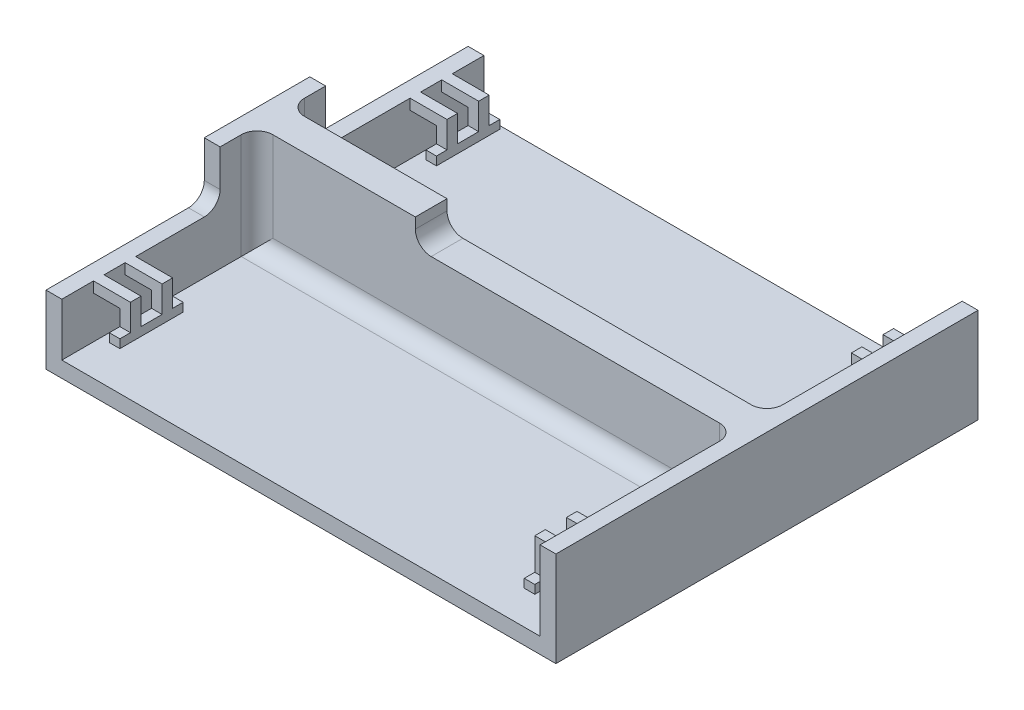
SolidWorks part; units mm, degrees
ref_plane "Piano frontale" through (0, 0, 0) normal (0, 0, 1) x (1, 0, 0)
ref_plane "Piano superiore" through (0, 0, 0) normal (0, 1, 0) x (1, 0, 0)
ref_plane "Piano destro" through (0, 0, 0) normal (1, 0, 0) x (0, 0, -1)
sketch "Schizzo1" plane through (0, 0, 0) normal (0, 0, 1) x (1, 0, 0)
  line L0 (11.7177, -12.3971) -> (506.3844, -12.3971) construction
  line L3 (25.2883, 10.9435) -> (25.2883, 30.9435)
  line L4 (118.9283, 25.9435) -> (118.9283, 7.9435)
  line L5 (118.9283, 7.9435) -> (22.2883, 7.9435)
  line L6 (115.9283, 25.9435) -> (115.9283, 10.9435)
  line L7 (115.9283, 10.9435) -> (25.2883, 10.9435)
  line L8 (22.2883, 7.9435) -> (22.2883, 30.9435)
  line L9 (22.2883, 30.9435) -> (25.2883, 30.9435)
  line L10 (115.9283, 25.9435) -> (118.9283, 25.9435)
  dimension "D1" = 90.64
  dimension "D2" = 20
  dimension "D3" = 15
  dimension "D4" = 3
extrude "Estrusione-Estrusione1" add sketch "Schizzo1" along normal blind 40
sketch "Schizzo2" plane through (25.2883, 0, 0) normal (1, 0, 0) x (0, 0, -1)
  line L0 (-40, 20.9435) -> (-10, 20.9435)
  line L1 (-40, 10.9435) -> (-40, 30.9435) construction
  line L2 (-10, 20.9435) -> (-10, 30.9435)
  line L3 (-40, 30.9435) -> (0, 30.9435) construction
  line L4 (-10, 30.9435) -> (-40, 30.9435)
  line L5 (-40, 30.9435) -> (-40, 20.9435)
  dimension "D1" = 30
  dimension "D2" = 10
extrude "Taglio-Estrusione2" cut sketch "Schizzo2" against normal blind 3
fillet "Raccordo1" radius 3 1 edges at (23.7883, 20.9435, 10)
sketch "Schizzo3" plane through (0, 0, 0) normal (0, 0, -1) x (-1, 0, 0)
  line L0 (-25.2883, 30.9435) -> (-55.2883, 30.9435)
  line L1 (-55.2883, 30.9435) -> (-55.2883, 25.9435)
  line L2 (-55.2883, 25.9435) -> (-115.9283, 25.9435)
  line L3 (-115.9283, 25.9435) -> (-115.9283, 10.9435)
  line L4 (-115.9283, 25.9435) -> (-115.9283, 10.9435) construction
  line L5 (-115.9283, 10.9435) -> (-25.2883, 10.9435) construction
  line L6 (-115.9283, 10.9435) -> (-25.2883, 10.9435)
  line L7 (-25.2883, 10.9435) -> (-25.2883, 30.9435)
  point P3 (-115.9283, 25.9435)
  dimension "D1" = 5
  dimension "D2" = 30
extrude "Estrusione-Estrusione2" add sketch "Schizzo3" against normal blind 3
mirror "Specchia1" about plane through (0, 0, 0) normal (0, 0, 1) of "Estrusione-Estrusione2", "Raccordo1", "Taglio-Estrusione2", "Estrusione-Estrusione1"
fillet "Raccordo2" radius 3 7 edges at (70.6083, 10.9435, 3) (70.6083, 10.9435, -3) (115.9283, 18.4435, -3) (115.9283, 18.4435, 3) (55.2883, 25.9435, 0) (25.2883, 20.9435, -3) (25.2883, 20.9435, 3)
sketch "Schizzo4" plane through (25.2883, 0, 0) normal (1, 0, 0) x (0, 0, -1)
  line L0 (-34, 20.9435) -> (-34, 18.9435)
  line L1 (-40, 20.9435) -> (-13, 20.9435) construction
  line L2 (-34, 18.9435) -> (-32, 18.9435)
  line L3 (-32, 18.9435) -> (-32, 20.9435)
  line L4 (-32, 20.9435) -> (-34, 20.9435)
  line L5 (-28, 20.9435) -> (-28, 18.9435)
  line L6 (-28, 18.9435) -> (-26, 18.9435)
  line L7 (-26, 18.9435) -> (-26, 20.9435)
  line L8 (-26, 20.9435) -> (-28, 20.9435)
  point P8 (-34.1109, 18.9435)
  dimension "D1" = 2
  dimension "D2" = 2
  dimension "D3" = 2
  dimension "D4" = 2
  dimension "D5" = 6
  dimension "D6" = 4
extrude "Estrusione-Estrusione3" add sketch "Schizzo4" along normal blind 7
sketch "Schizzo6" plane through (0, 18.9435, 0) normal (0, -1, 0) x (1, 0, 0)
  line L0 (32.2883, 34) -> (25.2883, 34) construction
  line L1 (30.2883, 34) -> (32.2883, 34)
  line L2 (30.2883, 34) -> (30.2883, 32)
  line L3 (30.2883, 32) -> (32.2883, 32)
  line L4 (32.2883, 34) -> (32.2883, 32)
  line L5 (32.2883, 28) -> (25.2883, 28) construction
  line L6 (30.2883, 28) -> (32.2883, 28)
  line L7 (30.2883, 28) -> (30.2883, 26)
  line L8 (30.2883, 26) -> (32.2883, 26)
  line L9 (32.2883, 28) -> (32.2883, 26)
  dimension "D1" = 2
  dimension "D2" = 2
extrude "Estrusione-Estrusione5" add sketch "Schizzo6" along normal blind 3
sketch "Schizzo7" plane through (0, 15.9435, 0) normal (0, -1, 0) x (1, 0, 0)
  line L0 (32.2883, 24) -> (32.2883, 36)
  line L1 (32.2883, 36) -> (30.2883, 36)
  line L2 (30.2883, 36) -> (30.2883, 24)
  line L3 (30.2883, 24) -> (32.2883, 24)
  line L4 (32.2883, 26) -> (32.2883, 28) construction
  line L6 (30.2883, 28) -> (30.2883, 26) construction
  point P2 (32.2369, 25.3039)
  dimension "D1" = 2
  dimension "D2" = 2
extrude "Estrusione-Estrusione6" add sketch "Schizzo7" along normal blind 1.62
sketch "Schizzo8" plane through (115.9283, 0, 0) normal (-1, 0, 0) x (0, 0, 1)
  line L0 (40, 10.9435) -> (6, 10.9435) construction
  line L1 (32, 18.9435) -> (34, 18.9435)
  line L2 (32, 18.9435) -> (32, 20.9435)
  line L3 (32, 20.9435) -> (34, 20.9435)
  line L4 (34, 18.9435) -> (34, 20.9435)
  line L5 (26, 20.9435) -> (28, 20.9435)
  line L6 (26, 20.9435) -> (26, 18.9435)
  line L7 (26, 18.9435) -> (28, 18.9435)
  line L8 (28, 20.9435) -> (28, 18.9435)
  line L9 (40, 25.9435) -> (40, 10.9435) construction
  dimension "D1" = 8
  dimension "D2" = 8
  dimension "D3" = 6
  dimension "D4" = 2
  dimension "D5" = 4
  dimension "D6" = 2
  dimension "D7" = 2
  dimension "D8" = 2
extrude "Estrusione-Estrusione7" add sketch "Schizzo8" along normal blind 7
sketch "Schizzo9" plane through (0, 18.9435, 0) normal (0, -1, 0) x (1, 0, 0)
  line L0 (108.9283, 32) -> (115.9283, 32) construction
  line L1 (108.9283, 34) -> (110.9283, 34)
  line L2 (108.9283, 34) -> (108.9283, 32)
  line L3 (108.9283, 32) -> (110.9283, 32)
  line L4 (110.9283, 34) -> (110.9283, 32)
  line L5 (108.9283, 26) -> (115.9283, 26) construction
  line L6 (108.9283, 28) -> (110.9283, 28)
  line L7 (108.9283, 28) -> (108.9283, 26)
  line L8 (108.9283, 26) -> (110.9283, 26)
  line L9 (110.9283, 28) -> (110.9283, 26)
  point P12 (111.0047, 26)
  dimension "D1" = 2
  dimension "D2" = 2
extrude "Estrusione-Estrusione8" add sketch "Schizzo9" along normal blind 4
sketch "Schizzo10" plane through (0, 14.9435, 0) normal (0, -1, 0) x (1, 0, 0)
  line L0 (108.9283, 36) -> (108.9283, 24)
  line L1 (108.9283, 24) -> (110.9283, 24)
  line L2 (110.9283, 24) -> (110.9283, 36)
  line L3 (110.9283, 36) -> (108.9283, 36)
  line L4 (110.9283, 32) -> (110.9283, 34) construction
  dimension "D1" = 2
  dimension "D2" = 2
extrude "Estrusione-Estrusione9" add sketch "Schizzo10" along normal blind 1.62
mirror "Specchia2" about plane through (0, 0, 0) normal (0, 0, 1) of "Estrusione-Estrusione3", "Estrusione-Estrusione5", "Estrusione-Estrusione6", "Estrusione-Estrusione7", "Estrusione-Estrusione8", "Estrusione-Estrusione9"
